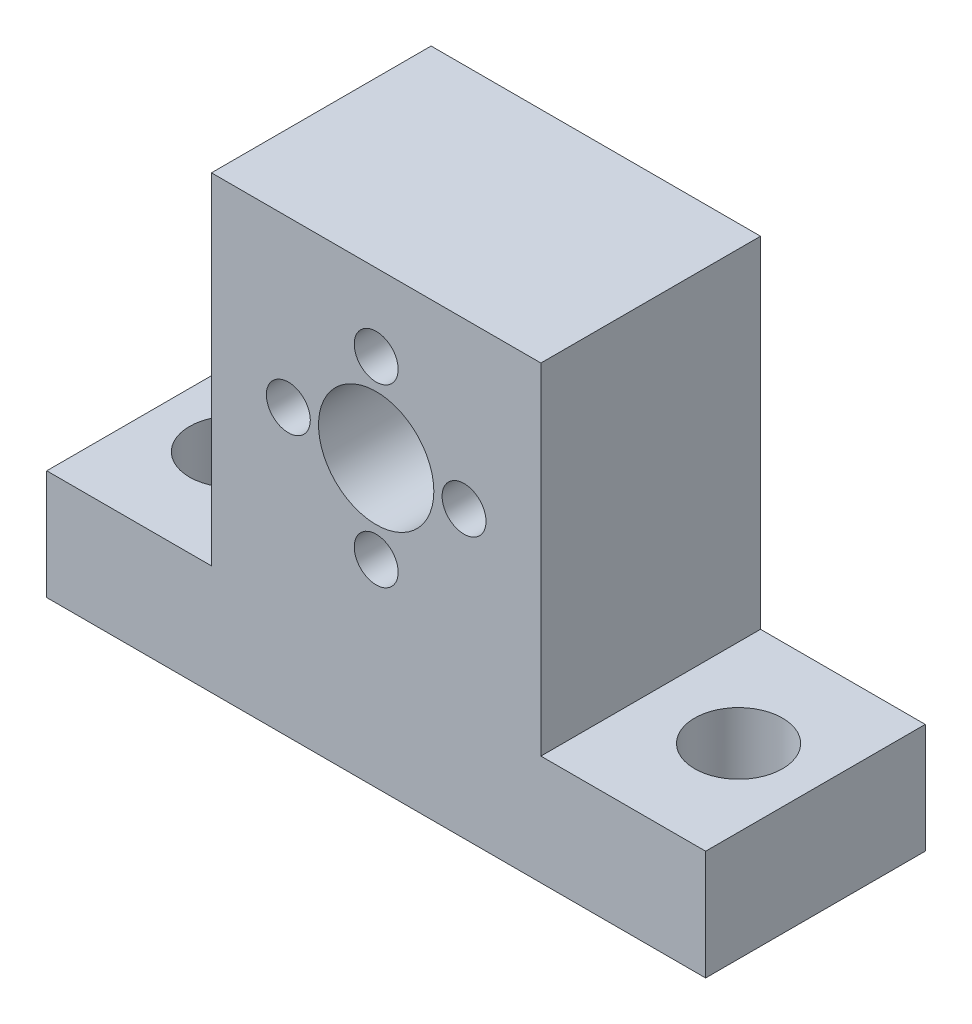
SolidWorks part; units mm, degrees
ref_plane "Front Plane" through (0, 0, 0) normal (0, 0, 1) x (1, 0, 0)
ref_plane "Top Plane" through (0, 0, 0) normal (0, 1, 0) x (1, 0, 0)
ref_plane "Right Plane" through (0, 0, 0) normal (1, 0, 0) x (0, 0, -1)
sketch "Sketch1" plane through (0, 0, 0) normal (0, 0, 1) x (1, 0, 0)
  line L0 (0, -438.3722) -> (0, 21480.2356) construction
  line L1 (-438.3722, 0) -> (21480.2356, 0) construction
  line L3 (-30, -26) -> (30, -26)
  line L4 (-30, -26) -> (-30, 15)
  line L5 (-30, 15) -> (30, 15)
  line L6 (30, -26) -> (30, 15)
  circle A0 centre (0, 0) radius 5.25
  circle A1 centre (0, 0) radius 8 construction
  circle A2 centre (0, 8) radius 2
  circle A3 centre (8, 0) radius 2
  circle A4 centre (0, -8) radius 2
  circle A5 centre (-8, 0) radius 2
  point P4 (0, 0)
  point P24 (0, 0)
  dimension "D2" = 10.5
  dimension "D4" = 16
  dimension "D5" = 4
  dimension "D7" = 8
  dimension "D8" = 8
  dimension "D1" = 15
  dimension "D3" = 60
  dimension "D9" = 26
  dimension "D10" = 30
  dimension "D6" = 4
extrude "Boss-Extrude1" add sketch "Sketch1" along normal blind 20
sketch "Sketch2" plane through (0, 15, 0) normal (0, 1, 0) x (1, 0, 0)
  line L0 (0, -1000) -> (0, 49000) construction
  line L1 (-1030, -10) -> (48970, -10) construction
  line L2 (-30, -20) -> (-30, 0) construction
  circle A0 centre (-23, -10) radius 4
  circle A1 centre (23, -10) radius 4
  point P8 (-30, -10)
  dimension "D2" = 8
  dimension "D1" = 7
extrude "Cut-Extrude1" cut sketch "Sketch2" against normal through all
sketch "Sketch3" plane through (0, 0, 0) normal (0, 0, -1) x (-1, 0, 0)
  line L0 (0, -1000) -> (0, 49000) construction
  line L1 (-1000, 0) -> (49000, 0) construction
  line L2 (-30, 15) -> (30, 15) construction
  line L3 (30, -26) -> (15, -26)
  line L4 (30, -26) -> (30, 15)
  line L5 (30, 15) -> (15, 15)
  line L6 (15, -26) -> (15, 15)
  line L7 (30, -16) -> (15, -16)
  line L8 (-30, -16) -> (-15, -16)
  line L9 (-15, -26) -> (-15, 15)
  line L10 (-30, 15) -> (-15, 15)
  line L11 (-30, -26) -> (-30, 15)
  line L12 (-30, -26) -> (-15, -26)
  line M7 (-30, 15) -> (-30, -26)
  line M10 (30, 15) -> (-30, 15)
  dimension "D1" = 15
  dimension "D2" = 10
extrude "Cut-Extrude2" cut sketch "Sketch3" against normal through all contours L7 L4 L6 M10 | L8 L9 M10 M7 region at (22.5, -0.5, 0) region at (-22.5, -0.5, 0)
